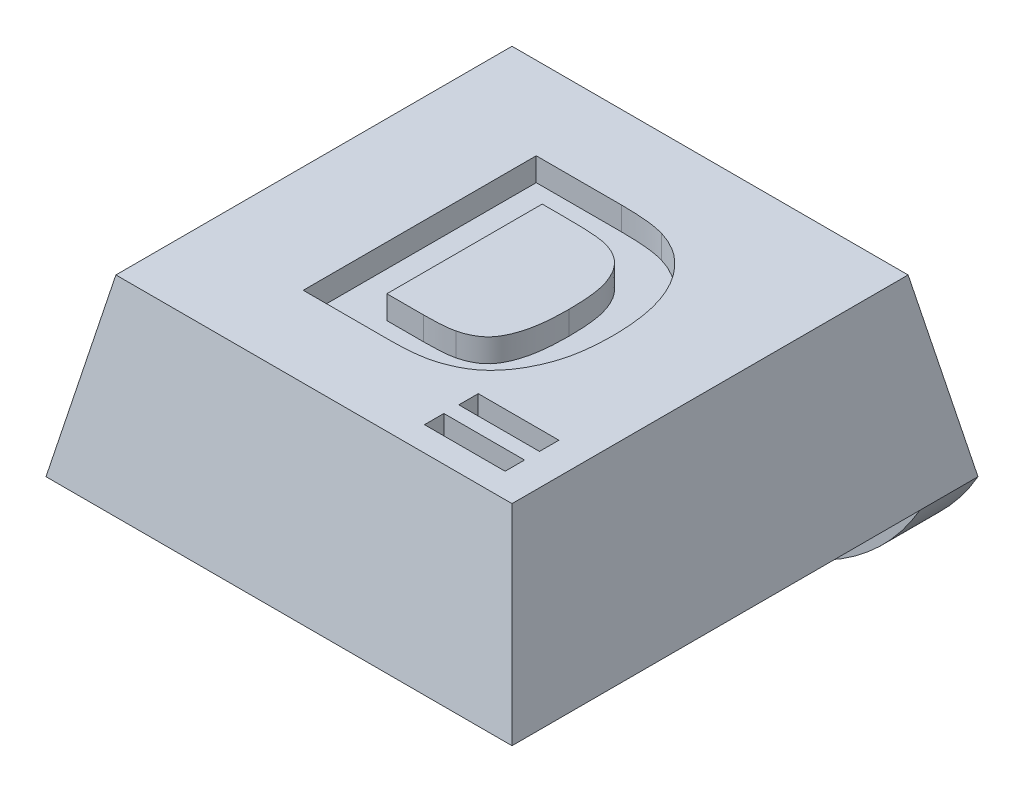
SolidWorks part; units mm, degrees
ref_plane "Front Plane" through (0, 0, 0) normal (0, 0, 1) x (1, 0, 0)
ref_plane "Top Plane" through (0, 0, 0) normal (0, 1, 0) x (1, 0, 0)
ref_plane "Right Plane" through (0, 0, 0) normal (1, 0, 0) x (0, 0, -1)
sketch "Sketch1" plane through (0, 0, 0) normal (0, 1, 0) x (1, 0, 0)
  line L1 (0, 0) -> (8, 0)
  line L2 (0, 0) -> (0, 8)
  line L3 (0, 8) -> (8, 8)
  line L4 (8, 0) -> (8, 8)
  dimension "D1" = 8
  dimension "D2" = 8
extrude "Boss-Extrude1" add sketch "Sketch1" along normal blind 3
sketch "Sketch2" plane through (0, 0, 0) normal (0, 0, 1) x (1, 0, 0)
  line L0 (0, 0) -> (0.6, 3)
  line L1 (0, 3) -> (8, 3) construction
  line L2 (0.6, 3) -> (0, 3)
  line L3 (0, 3) -> (0, 0)
  line L4 (8, 0) -> (7.4, 3)
  line L5 (7.4, 3) -> (8, 3)
  line L6 (8, 3) -> (8, 0)
  dimension "D1" = 0.6
  dimension "D2" = 0.6
extrude "Cut-Extrude1" cut sketch "Sketch2" against normal through all both and the other way through all
sketch "Sketch3" plane through (0, 0, 0) normal (1, 0, 0) x (0, 0, -1)
  line L0 (0, 0) -> (0.6, 3)
  line L1 (8, 3) -> (0, 3) construction
  line L2 (0.6, 3) -> (0, 3)
  line L3 (0, 3) -> (0, 0)
  line L4 (8, 3) -> (7.4, 3)
  line L5 (7.4, 3) -> (8, 0)
  line L6 (8, 3) -> (8, 0)
  dimension "D1" = 0.6
  dimension "D2" = 0.6
extrude "Cut-Extrude2" cut sketch "Sketch3" along normal blind 11
sketch "Sketch4" plane through (0, 0, 0) normal (0, -1, 0) x (1, 0, 0)
  line L0 (8, 0) -> (8, -8) construction
  line L3 (0, 0) -> (8, 0) construction
  circle A0 centre (4, -3.75) radius 1.8
  dimension "D1" = 3.6
  dimension "D2" = 4
  dimension "D3" = 3.75
extrude "Cut-Extrude3" cut sketch "Sketch4" against normal blind 0.8
sketch "Sketch5" plane through (0, 0, 0) normal (0, -1, 0) x (1, 0, 0)
  line L0 (8, 0) -> (8, -8) construction
  line L1 (0, -8) -> (8, -8)
  line L2 (0, -8) -> (0, -7)
  line L3 (0, -7) -> (8, -7)
  line L4 (8, -8) -> (8, -7)
  dimension "D1" = 1
extrude "Boss-Extrude2" add sketch "Sketch5" along normal blind 2
fillet "Fillet1" radius 4 2 edges at (8, -2, -7.5) (0, -2, -7.5)
sketch "Sketch6" plane through (0, 3, 0) normal (0, 1, 0) x (1, 0, 0)
  text T0 "D" font "Arial" height 4
extrude "Cut-Extrude4" cut sketch "Sketch6" against normal blind 0.4
sketch "Sketch7" plane through (0, 3, 0) normal (0, 1, 0) x (1, 0, 0)
  text T0 "=" font "Arial" height 2
extrude "Cut-Extrude5" cut sketch "Sketch7" against normal blind 0.4
